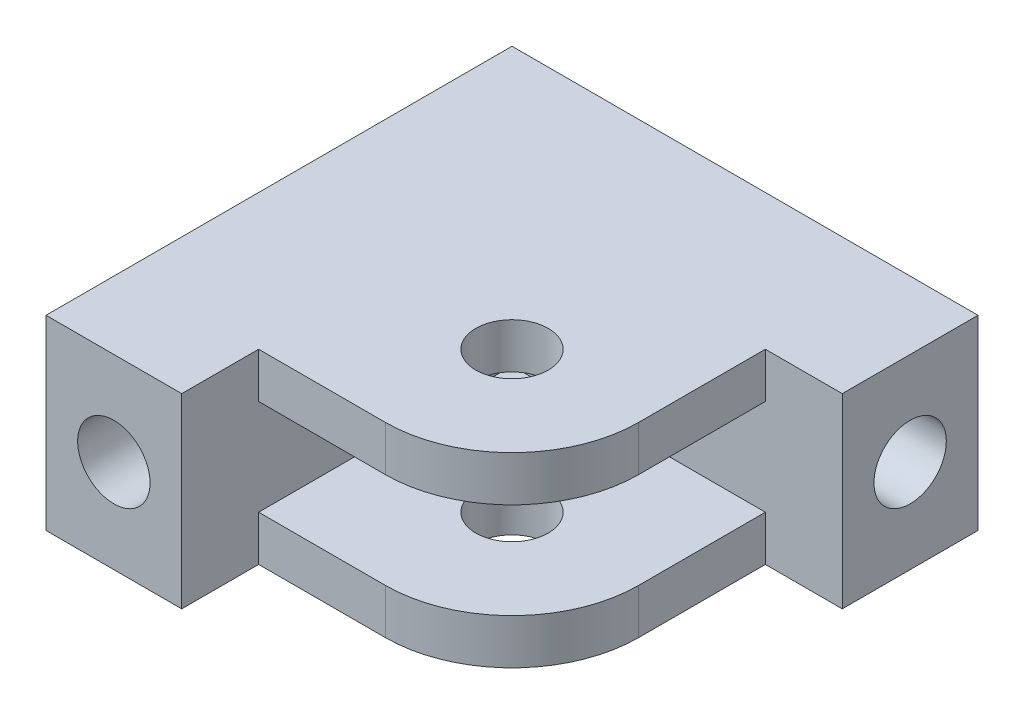
SolidWorks part; units mm, degrees
ref_plane "Front Plane" through (0, 0, 0) normal (0, 0, 1) x (1, 0, 0)
ref_plane "Top Plane" through (0, 0, 0) normal (0, 1, 0) x (1, 0, 0)
ref_plane "Right Plane" through (0, 0, 0) normal (1, 0, 0) x (0, 0, -1)
sketch "Sketch1" plane through (0, 0, 0) normal (0, 1, 0) x (1, 0, 0)
  line L0 (-49.9938, 47.1373) -> (-49.9938, 7.1373)
  line L1 (-53.4938, 58.6373) -> (-1.9938, 58.6373)
  line L2 (-53.4938, 58.6373) -> (-53.4938, 7.1373)
  line L3 (-53.4938, 7.1373) -> (-38.4938, 7.1373)
  line L4 (-1.9938, 58.6373) -> (-1.9938, 43.6373)
  line L5 (-41.9938, 55.1373) -> (-1.9938, 55.1373)
  line L6 (-41.9938, 55.1373) -> (-41.9938, 7.1373)
  line L7 (-49.9938, 47.1373) -> (-1.9938, 47.1373)
  line L8 (-38.4938, 7.1373) -> (-38.4938, 43.6373)
  line L9 (-1.9938, 43.6373) -> (-38.4938, 43.6373)
  line L10 (-24.4938, 15.6373) -> (-38.4938, 15.6373)
  line L11 (-10.4938, 29.6373) -> (-10.4938, 43.6373)
  arc A0 (-24.4938, 15.6373) -> (-10.4938, 29.6373) centre (-24.4938, 29.6373) ccw
  circle A1 centre (-24.4938, 29.6373) radius 4
  dimension "D9" = 28
  dimension "D10" = 8
  dimension "D1" = 40
  dimension "D2" = 40
  dimension "D3" = 3.5
  dimension "D4" = 3.5
  dimension "D5" = 8
  dimension "D6" = 8
  dimension "D7" = 3.5
  dimension "D8" = 3.5
extrude "Boss-Extrude1" add sketch "Sketch1" along normal blind 20.6 contours L0 L7 L6 L5 L4 L1 L2 L3 | L7 L0 L3 L6 | L9 L4 L7 L6 L3 L8 | L6 L7 L4 L5 region at (-45.9938, 0, -27.1373) region at (-50.7221, 0, -27.1373) region at (-21.9938, 0, -46.5717) region at (-21.9938, 0, -51.1373)
extrude "Boss-Extrude2" add sketch "Sketch1<3>" along normal blind 5 contours L10 A0 L11 L9 L8 A1 region at (-38.0978, 0, -29.6373)
sketch "Sketch1<3>" plane through (0, 0, 0) normal (0, 1, 0) x (1, 0, 0) same geometry as "Sketch1"
extrude "Boss-Extrude4" add sketch "Sketch1<4>" against normal blind 5 from vertex contours L10 A0 L11 L9 L8 A1 region at (-38.0978, 0, -29.6373) starting at point (-38.4938, 20.6, -43.6373)
sketch "Sketch1<4>" plane through (0, 0, 0) normal (0, 1, 0) x (1, 0, 0) same geometry as "Sketch1"
sketch "Sketch2" plane through (0, 0, -7.1373) normal (0, 0, 1) x (1, 0, 0)
  circle A0 centre (-45.9938, 10.3) radius 4
  dimension "D1" = 8
extrude "Cut-Extrude1" cut sketch "Sketch2" against normal up to vertex (40 mm away) up to point (-49.9938, 0, -47.1373)
chamfer "Chamfer1" distance 1 angle 45 1 edges at (-41.9938, 10.3, -47.1373)
sketch "Sketch5" plane through (-1.9938, 0, 0) normal (1, 0, 0) x (0, 0, -1)
  circle A0 centre (51.1373, 10.3) radius 4
  dimension "D1" = 8
extrude "Cut-Extrude7" cut sketch "Sketch5" against normal up to vertex (40 mm away) up to point (-41.9938, 0, -55.1373)
chamfer "Chamfer2" distance 1 angle 45 1 edges at (-41.9938, 10.3, -55.1373)
